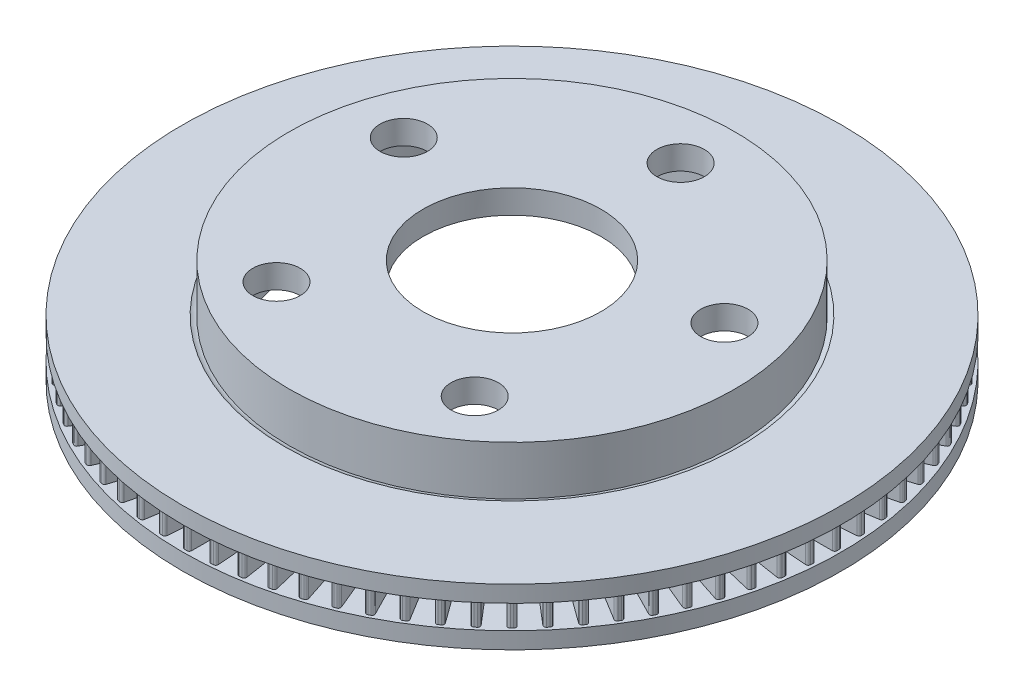
SolidWorks part; units mm, degrees
ref_plane "Front Plane" through (0, 0, 0) normal (0, 0, 1) x (1, 0, 0)
ref_plane "Top Plane" through (0, 0, 0) normal (0, 1, 0) x (1, 0, 0)
ref_plane "Right Plane" through (0, 0, 0) normal (1, 0, 0) x (0, 0, -1)
sketch "Sketch1" plane through (0, 0, 0) normal (0, 1, 0) x (1, 0, 0)
  circle A0 centre (0, 0) radius 139
  dimension "D1" = 278
extrude "Boss-Extrude1" add sketch "Sketch1" along normal blind 7
sketch "Sketch2" plane through (0, 7, 0) normal (0, 1, 0) x (1, 0, 0)
  circle A0 centre (0, 0) radius 86
  dimension "D1" = 172
extrude "Cut-Extrude1" cut sketch "Sketch2" against normal up to next
sketch "Sketch3" plane through (0, 7, 0) normal (0, 1, 0) x (1, 0, 0)
  line L0 (0, 156.3912) -> (0, -167.7382) construction
  line L1 (-176.6184, 0) -> (163.298, 0) construction
  line L3 (-87.5965, 1.5) -> (-136.5965, 1.5)
  line L4 (-86.5965, 0.5) -> (-86.5965, -0.5)
  line L5 (-87.5965, -1.5) -> (-136.5965, -1.5)
  line L6 (-137.5965, 0.5) -> (-137.5965, -0.5)
  line L7 (-86.5965, 1.5) -> (-137.5965, -1.5) construction
  line L8 (-86.5965, -1.5) -> (-137.5965, 1.5) construction
  arc A0 (-87.5965, 1.5) -> (-86.5965, 0.5) centre (-87.5965, 0.5) cw
  arc A1 (-86.5965, -0.5) -> (-87.5965, -1.5) centre (-87.5965, -0.5) cw
  arc A2 (-136.5965, -1.5) -> (-137.5965, -0.5) centre (-136.5965, -0.5) cw
  arc A3 (-136.5965, 1.5) -> (-137.5965, 0.5) centre (-136.5965, 0.5) ccw
  point P5 (-112.0965, 0)
  point P10 (0, 0)
  dimension "D1" = 51
  dimension "D2" = 1
  dimension "D3" = 3
extrude "Boss-Extrude2" add sketch "Sketch3" along normal blind 10
pattern_circular "CirPattern1" count 80 over 360 about axis through (0, 0, 0) along (0, 1, 0) of "Boss-Extrude2"
ref_plane "Plane1" through (0, 17, 0) normal (0, 1, 0) x (1, 0, 0)
sketch "Sketch5" plane through (0, 17, 0) normal (0, 1, 0) x (1, 0, 0)
  circle A0 centre (0, 0) radius 139
  dimension "D1" = 278
extrude "Boss-Extrude3" add sketch "Sketch5" along normal blind 7
sketch "Sketch6" plane through (0, 24, 0) normal (0, 1, 0) x (1, 0, 0)
  circle A0 centre (0, 0) radius 86
  dimension "D1" = 172
extrude "Cut-Extrude2" cut sketch "Sketch6" against normal up to next
sketch "Sketch7" plane through (0, 24, 0) normal (0, 1, 0) x (1, 0, 0)
  circle A0 centre (0, 0) radius 94
  dimension "D1" = 188
extrude "Boss-Extrude4" add sketch "Sketch7" along normal blind 20
sketch "Sketch8" plane through (0, 24, 0) normal (0, -1, 0) x (1, 0, 0)
  circle A0 centre (0, 0) radius 86
  dimension "D1" = 172
extrude "Cut-Extrude3" cut sketch "Sketch8" against normal blind 10
sketch "Sketch9" plane through (0, 44, 0) normal (0, 1, 0) x (1, 0, 0)
  circle A0 centre (0, 0) radius 37.5
  dimension "D1" = 75
extrude "Cut-Extrude4" cut sketch "Sketch9" against normal up to next
sketch "Sketch11" plane through (0, 44, 0) normal (0, 1, 0) x (1, 0, 0)
  line L0 (0, 164.145) -> (0, -166.5153) construction
  circle A0 centre (0, 71.1097) radius 10
  dimension "D1" = 20
extrude "Cut-Extrude7" cut sketch "Sketch11" against normal up to next
pattern_circular "CirPattern3" count 5 over 360 about axis through (0, 0, 0) along (0, 1, 0) of "Cut-Extrude7"
sketch "Sketch12" plane through (0, 0, 0) normal (1, 0, 0) x (0, 0, -1)
  line L0 (0, 106.267) -> (0, -70.5347) construction
  line L4 (94, 24) -> (94, 44) construction
  line L5 (94, 24.1235) -> (94, 23.3035)
  line L6 (94, 24.1235) -> (96.1921, 24.1235)
  arc A1 (96.1921, 24.1235) -> (94, 23.3035) centre (93.393, 28.2666) cw
  point P10 (94, 24.1235)
  dimension "D2" = 5
revolve "Cut-Revolve1" cut sketch "Sketch12" angle 360 about L0
